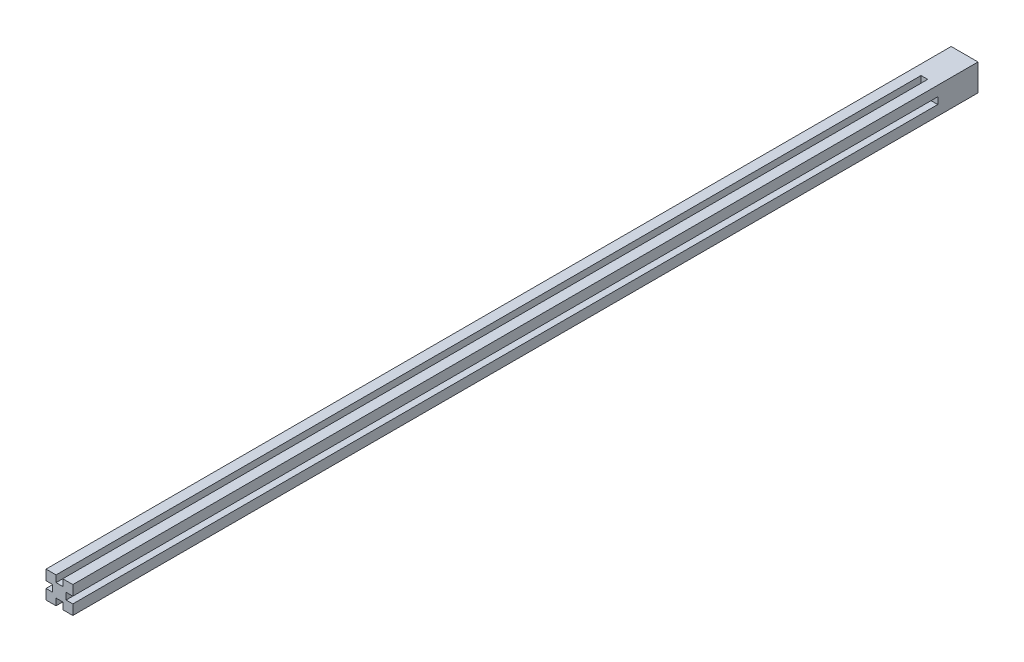
SolidWorks part; units mm, degrees
ref_plane "Front Plane" through (0, 0, 0) normal (0, 0, 1) x (1, 0, 0)
ref_plane "Top Plane" through (0, 0, 0) normal (0, 1, 0) x (1, 0, 0)
ref_plane "Right Plane" through (0, 0, 0) normal (1, 0, 0) x (0, 0, -1)
sketch "Sketch1" plane through (0, 0, 0) normal (0, 0, 1) x (1, 0, 0)
  line L1 (-10, 10) -> (10, 10)
  line L2 (-10, 10) -> (-10, -10)
  line L3 (-10, -10) -> (10, -10)
  line L4 (10, 10) -> (10, -10)
  line L5 (-10, 10) -> (10, -10) construction
  line L6 (-10, -10) -> (10, 10) construction
  line L7 (-2.5, 15) -> (2.5, 15)
  line L8 (-2.5, 15) -> (-2.5, 5)
  line L9 (-2.5, 5) -> (2.5, 5)
  line L10 (2.5, 15) -> (2.5, 5)
  line L11 (-2.5, 15) -> (2.5, 5) construction
  line L12 (-2.5, 5) -> (2.5, 15) construction
  point P0 (0, 0)
  point P6 (0, 10)
  dimension "D1" = 20
  dimension "D2" = 20
  dimension "D3" = 5
  dimension "D4" = 10
extrude "Boss-Extrude1" add sketch "Sketch1" against normal blind 675 contours L1 L10 L9 L8 L2 L3 L4 | L10 L1 L8 L9 region at (0, -0.5, 0) region at (0, 7.5, 0)
extrude "Cut-Extrude1" cut sketch "Sketch1<3>" against normal blind 645 contours L8 L9 L10 L7
sketch "Sketch1<3>" plane through (0, 0, 0) normal (0, 0, 1) x (1, 0, 0) same geometry as "Sketch1"
ref_axis "Axis1" through (0, 0, 32.25) along (0, 0, -1)
pattern_circular "CirPattern1" count 4 over 360 about axis through (0, 0, 32.25) along (0, 0, -1) of "Cut-Extrude1"
